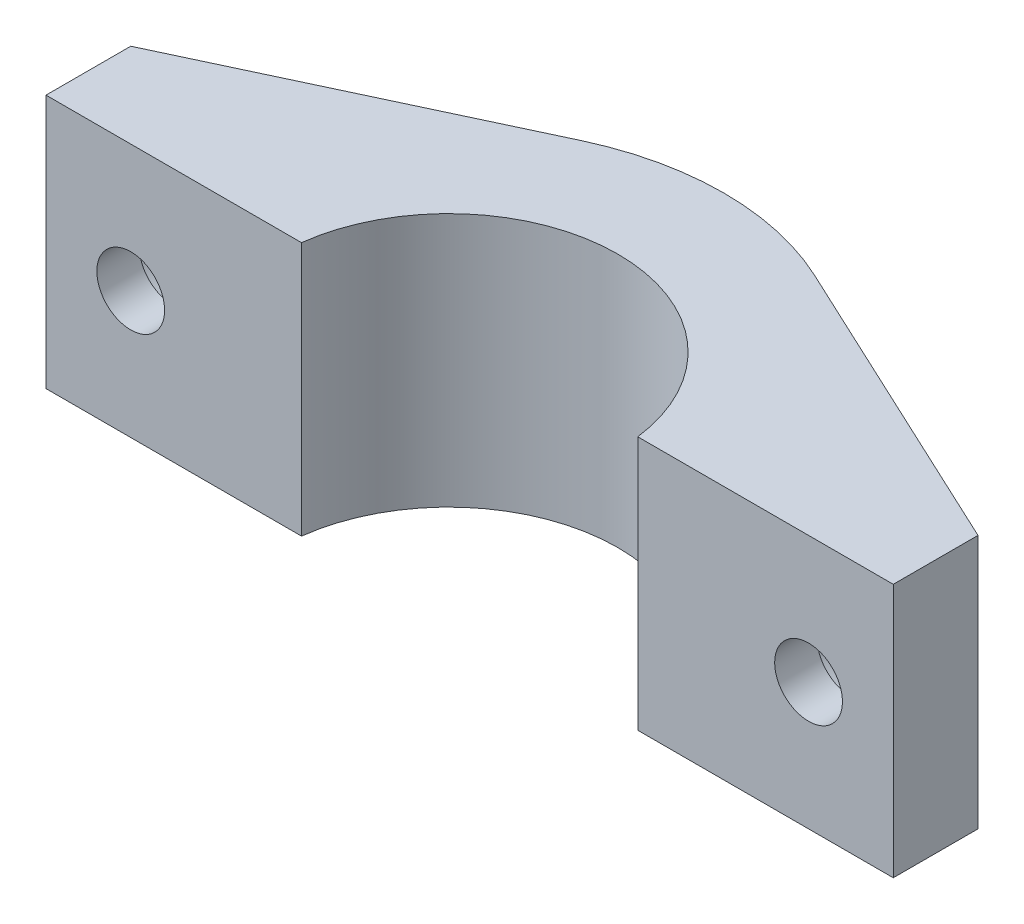
SolidWorks part; units mm, degrees
material "ABS"
ref_plane "Front Plane" through (0, 0, 0) normal (0, 0, 1) x (1, 0, 0)
ref_plane "Top Plane" through (0, 0, 0) normal (0, 1, 0) x (1, 0, 0)
ref_plane "Right Plane" through (0, 0, 0) normal (1, 0, 0) x (0, 0, -1)
sketch "Sketch1" plane through (0, 0, 0) normal (0, 1, 0) x (1, 0, 0)
  line L0 (20, 0) -> (-20, 0)
  line L1 (-20, 0) -> (-20, 5)
  line L2 (-20, 5) -> (20, 5)
  line L3 (20, 5) -> (20, 0)
  circle A0 centre (0, 0) radius 8
  circle A1 centre (0, 0) radius 14.5 construction
  circle A2 centre (0, 0) radius 13
  point P7 (0, 0)
  dimension "D1" = 16
  dimension "D2" = 26
  dimension "D3" = 1.5
  dimension "D4" = 40
  dimension "D5" = 5
extrude "Boss-Extrude1" add sketch "Sketch1" along normal blind 12 contours A2 L0 L3 L2 | L0 A2 L2 A0 | L2 A2 A0 | L2 A2 L0 A0 | A2 L2 L1 L0
sketch "Sketch2" plane through (0, 0, -5) normal (0, 0, -1) x (-1, 0, 0)
  line L0 (20, 12) -> (20, 0) construction
  circle A0 centre (16, 6) radius 1.6
  circle A1 centre (-16, 6) radius 1.6
  point P7 (20, 6)
  dimension "D3" = 3.2
  dimension "D1" = 32
  dimension "D2" = 16
extrude "Cut-Extrude1" cut sketch "Sketch2" against normal blind 12
sketch "Sketch3" plane through (0, 0, -5) normal (0, 0, -1) x (-1, 0, 0)
  circle A0 centre (16, 6) radius 3
  circle A1 centre (-16, 6) radius 3
  dimension "D1" = 6
extrude "Cut-Extrude2" cut sketch "Sketch3" against normal blind 2
sketch "Sketch4" plane through (0, 12, 0) normal (0, 1, 0) x (1, 0, 0)
  line L0 (-20, 5) -> (-5.5059, 11.7765)
  line L1 (-20, 5) -> (-12, 5)
  line L2 (-12, 5) -> (-3.4374, 7.3521)
  line L3 (-3.4374, 7.3521) -> (-5.5059, 11.7765)
  arc A0 (12, 5) -> (-12, 5) centre (0, 0) ccw construction
  arc A1 (8, 0) -> (-8, 0) centre (0, 0) ccw construction
extrude "Boss-Extrude2" add sketch "Sketch4" against normal blind 2
mirror "Mirror1" about plane through (0, 0, 0) normal (1, 0, 0) of "Boss-Extrude2"
ref_plane "Plane1" through (0, 6, 0) normal (0, 1, 0) x (1, 0, 0)
mirror "Mirror2" about plane through (0, 6, 0) normal (0, 1, 0) of "Boss-Extrude2", "Mirror1"
chamfer "Chamfer1" distance 5 2 edges at (-12, 6, -5) (12, 6, -5)
sketch "Sketch5" plane through (0, 0, 0) normal (0, -1, 0) x (1, 0, 0)
  line L0 (-20, 0) -> (-20, -5) construction
  line L1 (20, 0) -> (-20, 0)
  line L2 (20, 0) -> (20, -1)
  line L3 (20, -1) -> (-20, -1)
  line L4 (-20, 0) -> (-20, -1)
  dimension "D1" = 1
extrude "Cut-Extrude3" cut sketch "Sketch5" against normal blind 20
equation "\"D2@Sketch2\"=\"D1@Sketch2\"/2"
